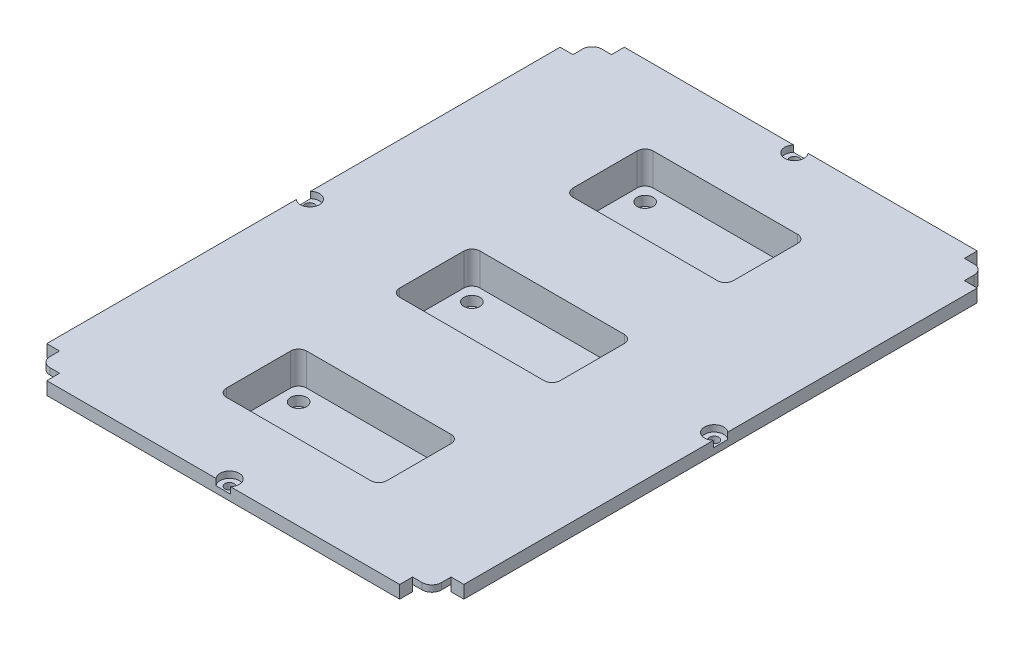
SolidWorks part; units mm, degrees
ref_plane "Спереди" through (0, 0, 0) normal (0, 0, 1) x (1, 0, 0)
ref_plane "Сверху" through (0, 0, 0) normal (0, 1, 0) x (1, 0, 0)
ref_plane "Справа" through (0, 0, 0) normal (1, 0, 0) x (0, 0, -1)
sketch "Эскиз1" plane through (0, 0, 0) normal (0, 1, 0) x (1, 0, 0)
  line L1 (-65, -90) -> (65, -90)
  line L2 (-65, -90) -> (-65, 90)
  line L3 (-65, 90) -> (65, 90)
  line L4 (65, -90) -> (65, 90)
  line L5 (-65, -90) -> (65, 90) construction
  line L6 (-65, 90) -> (65, -90) construction
  point P0 (0, 0)
  dimension "D1" = 130
  dimension "D2" = 180
extrude "Бобышка-Вытянуть1" add sketch "Эскиз1" along normal blind 55
sketch "Эскиз2" plane through (0, 0, 90) normal (0, 0, 1) x (1, 0, 0)
  line L0 (-1050, 27.5) -> (48950, 27.5) construction
  line L1 (-65, 55) -> (-65, 0) construction
  line L2 (0, -999.2777) -> (0, 49000.7223) construction
  line L4 (-22.5, 15) -> (22.5, 15)
  line L5 (-25, 17.5) -> (-25, 37.5)
  line L6 (-22.5, 40) -> (22.5, 40)
  line L7 (25, 17.5) -> (25, 37.5)
  line L8 (-25, 15) -> (25, 40) construction
  line L9 (-25, 40) -> (25, 15) construction
  arc A0 (-22.5, 40) -> (-25, 37.5) centre (-22.5, 37.5) ccw
  arc A1 (-25, 17.5) -> (-22.5, 15) centre (-22.5, 17.5) ccw
  arc A2 (25, 17.5) -> (22.5, 15) centre (22.5, 17.5) cw
  arc A3 (25, 37.5) -> (22.5, 40) centre (22.5, 37.5) ccw
  point P5 (-65, 27.5)
  point P6 (0, 27.5)
  dimension "D3" = 2.5
  dimension "D4" = 2.5
  dimension "D1" = 25
  dimension "D2" = 50
extrude "Вырез-Вытянуть1" cut sketch "Эскиз2" against normal blind 10
sketch "Эскиз4" plane through (0, 55, 0) normal (0, 1, 0) x (1, 0, 0)
  line L0 (0, -1000) -> (0, 49000) construction
  line L1 (-1000, 0) -> (49000, 0) construction
  line L2 (-22.5, 41.5) -> (22.5, 41.5)
  line L3 (-25, 44) -> (-25, 64)
  line L4 (-22.5, 66.5) -> (22.5, 66.5)
  line L5 (-22.5, -12.5) -> (22.5, -12.5)
  line L6 (-25, -10) -> (-25, 10)
  line L7 (-22.5, 12.5) -> (22.5, 12.5)
  line L8 (25, -10) -> (25, 10)
  line L9 (-25, -12.5) -> (25, 12.5) construction
  line L10 (-25, 12.5) -> (25, -12.5) construction
  line L11 (25, 44) -> (25, 64)
  line L12 (-25, 41.5) -> (25, 66.5) construction
  line L13 (-25, 66.5) -> (25, 41.5) construction
  line L14 (-25, -12.5) -> (25, -12.5) [skipped]
  line L15 (-25, -12.5) -> (-25, 12.5) [skipped]
  line L16 (-25, 12.5) -> (25, 12.5) [skipped]
  line L17 (25, -12.5) -> (25, 12.5) [skipped]
  line L18 (-25, -12.5) -> (25, 12.5) construction
  line L19 (-25, 12.5) -> (25, -12.5) construction
  line L20 (-22.5, -66.5) -> (22.5, -66.5)
  line L21 (-25, -64) -> (-25, -44)
  line L22 (-22.5, -41.5) -> (22.5, -41.5)
  line L23 (25, -64) -> (25, -44)
  line L24 (-25, -66.5) -> (25, -41.5) construction
  line L25 (-25, -41.5) -> (25, -66.5) construction
  arc A0 (22.5, -41.5) -> (25, -44) centre (22.5, -44) cw
  arc A1 (25, -64) -> (22.5, -66.5) centre (22.5, -64) cw
  arc A2 (-22.5, -66.5) -> (-25, -64) centre (-22.5, -64) cw
  arc A3 (-25, -44) -> (-22.5, -41.5) centre (-22.5, -44) cw
  arc A4 (-25, 64) -> (-22.5, 66.5) centre (-22.5, 64) cw
  arc A5 (-22.5, 12.5) -> (-25, 10) centre (-22.5, 10) ccw
  arc A6 (25, -10) -> (22.5, -12.5) centre (22.5, -10) cw
  arc A7 (22.5, 66.5) -> (25, 64) centre (22.5, 64) cw
  arc A8 (25, 44) -> (22.5, 41.5) centre (22.5, 44) cw
  arc A9 (-22.5, 41.5) -> (-25, 44) centre (-22.5, 44) cw
  arc A10 (22.5, 12.5) -> (25, 10) centre (22.5, 10) cw
  arc A11 (-22.5, -12.5) -> (-25, -10) centre (-22.5, -10) cw
  point P8 (0, 0)
  point P9 (0, 54)
  point P18 (0, 0)
  point P23 (0, -54)
  dimension "D7" = 2.5
  dimension "D8" = 2.5
  dimension "D1" = 25
  dimension "D2" = 50
  dimension "D5" = 41.5
  dimension "D6" = 41.5
  dimension "D3" = 2
  dimension "D4" = 2
extrude "Вырез-Вытянуть2" cut sketch "Эскиз4" against normal blind 10
mirror "Зеркальное отражение1" about plane through (0, 0, 0) normal (0, 0, 1) of "Вырез-Вытянуть1"
shell "Оболочка1" thickness 4 removed face at (0, 0, 0)
sketch "Эскиз5" plane through (-65, 0, 0) normal (-1, 0, 0) x (0, 0, 1)
  line L0 (45, 28.75) -> (45, 11.25) construction
  line L2 (90, 55) -> (90, 0) construction
  line L4 (-90, 0) -> (90, 0) construction
  line L7 (-1075, 20) -> (48925, 20) construction
  line L8 (-90, 55) -> (-90, 0) construction
  circle A3 centre (45, 28.75) radius 1.45
  circle A4 centre (45, 11.25) radius 1.45
  circle A5 centre (65.6, 20) radius 4
  circle A6 centre (-65.6, 20) radius 5
  dimension "D2" = 17.5
  dimension "D3" = 20
  dimension "D6" = 10
  dimension "D1" = 17.5
  dimension "D5" = 2.9
  dimension "D9" = 45
  dimension "D10" = 20.6
  dimension "D11" = 8
  dimension "D4" = 24.4
extrude "Вырез-Вытянуть3" cut sketch "Эскиз5" against normal blind 15
sketch "Эскиз6" plane through (-65, 0, 0) normal (-1, 0, 0) x (0, 0, 1)
  circle A2 centre (45, 28.75) radius 3
  circle A3 centre (45, 11.25) radius 3
  dimension "D1" = 6
extrude "Вырез-Вытянуть4" cut sketch "Эскиз6" against normal blind 2.5
sketch "Эскиз11" plane through (-61, 0, 0) normal (1, 0, 0) x (0, 0, -1)
  circle A1 centre (-65.6, 20) radius 5
  dimension "D1" = 10
extrude "Вырез-Вытянуть16" cut sketch "Эскиз11" against normal blind 1
mirror "Зеркальное отражение2" about plane through (0, 0, 0) normal (1, 0, 0) of "Вырез-Вытянуть3", "Вырез-Вытянуть4", "Вырез-Вытянуть16"
sketch "Эскиз12" plane through (0, 11, 0) normal (0, -1, 0) x (-1, 0, 0)
  line L0 (-1014.7864, -78) -> (48985.2136, -78) construction
  line L1 (22.5, -76) -> (-22.5, -76) construction
  line L2 (0, -1061) -> (0, 48939) construction
  line L3 (-10, -1061) -> (-10, 48939) construction
  line L4 (10, -1061) -> (10, 48939) construction
  circle A0 centre (-10, -78) radius 1.45
  circle A1 centre (10, -78) radius 1.45
  point P7 (0, -76)
  dimension "D4" = 2.9
  dimension "D1" = 2
  dimension "D2" = 20
  dimension "D3" = 10
extrude "Вырез-Вытянуть17" cut sketch "Эскиз12" against normal blind 14
sketch "Эскиз15" plane through (0, 45, 0) normal (0, 1, 0) x (1, 0, 0)
  line L0 (-1010.1672, -62.5) -> (48989.8328, -62.5) construction
  line L1 (0, -1031.5) -> (0, 48968.5) construction
  line L2 (-7.6, -63.8) -> (7.6, -63.8)
  line L3 (-7.6, -63.8) -> (-7.6, -61.2)
  line L4 (-7.6, -61.2) -> (7.6, -61.2)
  line L5 (7.6, -63.8) -> (7.6, -61.2)
  line L6 (-7.6, -63.8) -> (7.6, -61.2) construction
  line L7 (-7.6, -61.2) -> (7.6, -63.8) construction
  line L8 (22.5, -41.5) -> (-22.5, -41.5) construction
  line L9 (-22.5, -66.5) -> (22.5, -66.5) construction
  line L10 (-7.6, -9.8) -> (7.6, -9.8)
  line L11 (-7.6, -9.8) -> (-7.6, -7.2)
  line L12 (-7.6, -7.2) -> (7.6, -7.2)
  line L13 (7.6, -9.8) -> (7.6, -7.2)
  line L14 (-7.6, -9.8) -> (7.6, -7.2) construction
  line L15 (-7.6, -7.2) -> (7.6, -9.8) construction
  line L16 (-7.6, 44.2) -> (7.6, 44.2)
  line L17 (-7.6, 44.2) -> (-7.6, 46.8)
  line L18 (-7.6, 46.8) -> (7.6, 46.8)
  line L19 (7.6, 44.2) -> (7.6, 46.8)
  line L20 (-7.6, 44.2) -> (7.6, 46.8) construction
  line L21 (-7.6, 46.8) -> (7.6, 44.2) construction
  line L23 (22.5, 12.5) -> (-22.5, 12.5) construction
  line L24 (-7.6, -59.8) -> (7.6, -59.8)
  line L25 (-7.6, -59.8) -> (-7.6, -57.2)
  line L26 (-7.6, -57.2) -> (7.6, -57.2)
  line L27 (7.6, -59.8) -> (7.6, -57.2)
  line L28 (-7.6, -59.8) -> (7.6, -57.2) construction
  line L29 (-7.6, -57.2) -> (7.6, -59.8) construction
  line L30 (-7.6, -5.8) -> (7.6, -5.8)
  line L31 (-7.6, -5.8) -> (-7.6, -3.2)
  line L32 (-7.6, -3.2) -> (7.6, -3.2)
  line L33 (7.6, -5.8) -> (7.6, -3.2)
  line L34 (-7.6, -5.8) -> (7.6, -3.2) construction
  line L35 (-7.6, -3.2) -> (7.6, -5.8) construction
  line L36 (-7.6, 48.2) -> (7.6, 48.2)
  line L37 (-7.6, 48.2) -> (-7.6, 50.8)
  line L38 (-7.6, 50.8) -> (7.6, 50.8)
  line L39 (7.6, 48.2) -> (7.6, 50.8)
  line L40 (-7.6, 48.2) -> (7.6, 50.8) construction
  line L41 (-7.6, 50.8) -> (7.6, 48.2) construction
  line L42 (-22.5, -12.5) -> (22.5, -12.5) construction
  circle A0 centre (-20, -46.5) radius 2.5
  circle A1 centre (20, -46.5) radius 2.5
  circle A2 centre (-20, 7.5) radius 2.5
  circle A3 centre (20, 7.5) radius 2.5
  circle A4 centre (-20, 61.5) radius 2.5
  circle A5 centre (20, 61.5) radius 2.5
  point P1 (0, -62.5)
  point P12 (0, -41.5)
  point P16 (0, -8.5)
  point P21 (0, 45.5)
  point P41 (0, -4.5)
  point P42 (0, -58.5)
  point P51 (0, 49.5)
  dimension "D6" = 40
  dimension "D8" = 5
  dimension "D1" = 2.6
  dimension "D2" = 15.2
  dimension "D3" = 4
  dimension "D4" = 3
  dimension "D5" = 4
  dimension "D7" = 40
  dimension "D9" = 5
  dimension "D10" = 3
  dimension "D11" = 5
  dimension "D13" = 4
  dimension "D15" = 4
  dimension "D12" = 2
  dimension "D14" = 3
extrude "Вырез-Вытянуть20" cut sketch "Эскиз15" against normal blind 3
sketch "Эскиз16" plane through (0, 42, 0) normal (0, 1, 0) x (1, 0, 0)
  line L0 (-7.6, -62.5) -> (7.6, -62.5) construction
  line L1 (-7.6, -61.2) -> (-7.6, -63.8) construction
  line L2 (7.6, -63.8) -> (7.6, -61.2) construction
  line L3 (0, -1000) -> (0, 49000) construction
  line L4 (-7, -63.4) -> (7, -63.4)
  line L5 (-7, -63.4) -> (-7, -61.6)
  line L6 (-7, -61.6) -> (7, -61.6)
  line L7 (7, -63.4) -> (7, -61.6)
  line L8 (-7, -63.4) -> (7, -61.6) construction
  line L9 (-7, -61.6) -> (7, -63.4) construction
  line L10 (-7, -9.4) -> (7, -9.4)
  line L11 (-7, -9.4) -> (-7, -7.6)
  line L12 (-7, -7.6) -> (7, -7.6)
  line L13 (7, -9.4) -> (7, -7.6)
  line L14 (-7.6, -8.5) -> (7.6, -8.5) construction
  line L15 (-7, -9.4) -> (7, -7.6) construction
  line L16 (-7, -7.6) -> (7, -9.4) construction
  line L17 (-7, 44.6) -> (7, 44.6)
  line L18 (-7, 44.6) -> (-7, 46.4)
  line L19 (-7, 46.4) -> (7, 46.4)
  line L20 (7, 44.6) -> (7, 46.4)
  line L21 (-7.6, 45.5) -> (7.6, 45.5) construction
  line L22 (-7, 44.6) -> (7, 46.4) construction
  line L23 (-7, 46.4) -> (7, 44.6) construction
  line L24 (-7.6, -7.2) -> (-7.6, -9.8) construction
  line L25 (-7.6, -58.5) -> (7.6, -58.5) construction
  line L26 (-7, -59.4) -> (7, -59.4)
  line L27 (-7, -59.4) -> (-7, -57.6)
  line L28 (-7, -57.6) -> (7, -57.6)
  line L29 (7, -59.4) -> (7, -57.6)
  line L30 (-7, -59.4) -> (7, -57.6) construction
  line L31 (-7, -57.6) -> (7, -59.4) construction
  line L32 (-7.6, -57.2) -> (-7.6, -59.8) construction
  line L33 (7.6, -59.8) -> (7.6, -57.2) construction
  line L34 (-7.6, -4.5) -> (7.6, -4.5) construction
  line L35 (-7.6, -3.2) -> (-7.6, -5.8) construction
  line L36 (7.6, -5.8) -> (7.6, -3.2) construction
  line L37 (-7.6, -9.8) -> (7.6, -9.8) construction
  line L38 (-7, -5.4) -> (7, -5.4)
  line L39 (-7, -5.4) -> (-7, -3.6)
  line L40 (-7, -3.6) -> (7, -3.6)
  line L41 (7, -5.4) -> (7, -3.6)
  line L42 (-7, -5.4) -> (7, -3.6) construction
  line L43 (-7, -3.6) -> (7, -5.4) construction
  line L44 (7.6, -9.8) -> (7.6, -7.2) construction
  line L45 (-7.6, 46.8) -> (-7.6, 44.2) construction
  line L46 (7.6, 44.2) -> (7.6, 46.8) construction
  line L47 (-7.6, 44.2) -> (7.6, 44.2) construction
  line L48 (-7.6, 49.5) -> (7.6, 49.5) construction
  line L49 (-7.6, 50.8) -> (-7.6, 48.2) construction
  line L50 (7.6, 48.2) -> (7.6, 50.8) construction
  line L52 (-7, 48.6) -> (7, 48.6)
  line L53 (-7, 48.6) -> (-7, 50.4)
  line L54 (-7, 50.4) -> (7, 50.4)
  line L55 (7, 48.6) -> (7, 50.4)
  line L56 (-7, 48.6) -> (7, 50.4) construction
  line L57 (-7, 50.4) -> (7, 48.6) construction
  point P6 (0, -62.5)
  point P12 (0, -58.5)
  point P17 (0, -8.5)
  point P24 (0, 36.6)
  point P41 (0, -4.5)
  point P54 (0, 49.5)
  dimension "D1" = 1.8
  dimension "D2" = 14
  dimension "D4" = 0.4
  dimension "D3" = 0.4
extrude "Вырез-Вытянуть21" cut sketch "Эскиз16" against normal blind 3
sketch "Эскиз17" plane through (0, 0, 80) normal (0, 0, 1) x (1, 0, 0)
  line L0 (-7.6, 17.5) -> (7.6, 17.5)
  line L1 (-7.6, 17.5) -> (-7.6, 20.1)
  line L2 (-7.6, 20.1) -> (7.6, 20.1)
  line L3 (7.6, 17.5) -> (7.6, 20.1)
  line L4 (-7.6, 17.5) -> (7.6, 20.1) construction
  line L5 (-7.6, 20.1) -> (7.6, 17.5) construction
  line L7 (-7.6, 21.5) -> (7.6, 21.5)
  line L8 (-22.5, 15) -> (22.5, 15) construction
  line L9 (0, -965) -> (0, 49035) construction
  line L10 (22.5, 40) -> (-22.5, 40) construction
  line L11 (-7.6, 21.5) -> (-7.6, 24.1)
  line L12 (-7.6, 24.1) -> (7.6, 24.1)
  line L13 (7.6, 21.5) -> (7.6, 24.1)
  line L14 (-7.6, 21.5) -> (7.6, 24.1) construction
  line L15 (-7.6, 24.1) -> (7.6, 21.5) construction
  circle A0 centre (-20, 35) radius 2.5
  circle A1 centre (20, 35) radius 2.5
  point P0 (0, 18.8)
  point P11 (0, 22.8)
  point P20 (0, 40)
  dimension "D5" = 5
  dimension "D8" = 4
  dimension "D1" = 2.6
  dimension "D2" = 15.2
  dimension "D3" = 40
  dimension "D4" = 40
  dimension "D6" = 2.5
  dimension "D7" = 5
extrude "Вырез-Вытянуть22" cut sketch "Эскиз17" against normal blind 3
sketch "Эскиз18" plane through (0, 0, 77) normal (0, 0, 1) x (1, 0, 0)
  line L0 (-7.6, 18.8) -> (7.6, 18.8) construction
  line L1 (-7.6, 20.1) -> (-7.6, 17.5) construction
  line L2 (7.6, 17.5) -> (7.6, 20.1) construction
  line L3 (0, -980.9) -> (0, 49019.1) construction
  line L4 (-7, 17.9) -> (7, 17.9)
  line L5 (-7, 17.9) -> (-7, 19.7)
  line L6 (-7, 19.7) -> (7, 19.7)
  line L7 (7, 17.9) -> (7, 19.7)
  line L8 (-7, 17.9) -> (7, 19.7) construction
  line L9 (-7, 19.7) -> (7, 17.9) construction
  line L10 (7.6, 24.1) -> (-7.6, 24.1) construction
  line L12 (-7, 21.9) -> (7, 21.9)
  line L13 (-7, 21.9) -> (-7, 23.7)
  line L14 (-7, 23.7) -> (7, 23.7)
  line L15 (7, 21.9) -> (7, 23.7)
  line L16 (-7, 21.9) -> (7, 23.7) construction
  line L17 (-7, 23.7) -> (7, 21.9) construction
  point P6 (0, 18.8)
  point P12 (0, 22.8)
  point P16 (0, 24.1)
  dimension "D1" = 1.8
  dimension "D2" = 14
  dimension "D3" = 4
extrude "Вырез-Вытянуть23" cut sketch "Эскиз18" against normal blind 3
sketch "Эскиз19" plane through (0, 0, -80) normal (0, 0, -1) x (1, 0, 0)
  line L0 (-7.6, -37.5) -> (7.6, -37.5)
  line L1 (-7.6, -37.5) -> (-7.6, -34.9)
  line L2 (-7.6, -34.9) -> (7.6, -34.9)
  line L3 (7.6, -37.5) -> (7.6, -34.9)
  line L4 (-7.6, -37.5) -> (7.6, -34.9) construction
  line L5 (-7.6, -34.9) -> (7.6, -37.5) construction
  line L6 (0, -1010) -> (0, 48990) construction
  line L7 (-22.5, -15) -> (22.5, -15) construction
  line L9 (-7.6, -33.5) -> (7.6, -33.5)
  line L10 (22.5, -40) -> (-22.5, -40) construction
  line L11 (-7.6, -33.5) -> (-7.6, -30.9)
  line L12 (-7.6, -30.9) -> (7.6, -30.9)
  line L13 (7.6, -33.5) -> (7.6, -30.9)
  line L14 (-7.6, -33.5) -> (7.6, -30.9) construction
  line L15 (-7.6, -30.9) -> (7.6, -33.5) construction
  circle A0 centre (-20, -20) radius 2.5
  circle A1 centre (20, -20) radius 2.5
  point P0 (0, -36.2)
  point P14 (0, -15)
  point P16 (0, -32.2)
  dimension "D5" = 5
  dimension "D7" = 2.5
  dimension "D1" = 2.6
  dimension "D2" = 15.2
  dimension "D3" = 40
  dimension "D4" = 40
  dimension "D6" = 5
  dimension "D8" = 4
extrude "Вырез-Вытянуть24" cut sketch "Эскиз19" against normal blind 3
sketch "Эскиз20" plane through (0, 0, -77) normal (0, 0, -1) x (1, 0, 0)
  line L0 (-1007.6, -36.2) -> (48992.4, -36.2) construction
  line L1 (-7.6, -34.9) -> (-7.6, -37.5) construction
  line L3 (-7, -37.1) -> (7, -37.1)
  line L4 (-7, -37.1) -> (-7, -35.3)
  line L5 (-7, -35.3) -> (7, -35.3)
  line L6 (7, -37.1) -> (7, -35.3)
  line L7 (-7, -37.1) -> (7, -35.3) construction
  line L8 (-7, -35.3) -> (7, -37.1) construction
  line L9 (-7, -31.3) -> (7, -31.3)
  line L10 (0, -1029.9) -> (0, 48970.1) construction
  line L11 (7.6, -34.9) -> (-7.6, -34.9) construction
  line L12 (-7, -31.3) -> (-7, -33.1)
  line L13 (-7, -33.1) -> (7, -33.1)
  line L14 (7, -31.3) -> (7, -33.1)
  line L15 (-7, -31.3) -> (7, -33.1) construction
  line L16 (-7, -33.1) -> (7, -31.3) construction
  point P1 (0, -36.2)
  point P5 (-7.6, -36.2)
  point P10 (0, -32.2)
  point P18 (0, -34.9)
  dimension "D1" = 1.8
  dimension "D2" = 14
  dimension "D3" = 4
extrude "Вырез-Вытянуть25" cut sketch "Эскиз20" against normal blind 5
sketch "Эскиз21" plane through (0, 0, 90) normal (0, 0, -1) x (1, 0, 0)
  line L0 (-975, -27.5) -> (49025, -27.5) construction
  line L1 (35.25, -34.75) -> (44.75, -34.75)
  line L2 (35.25, -34.75) -> (35.25, -20.25)
  line L3 (35.25, -20.25) -> (44.75, -20.25)
  line L4 (44.75, -34.75) -> (44.75, -20.25)
  line L5 (35.25, -34.75) -> (44.75, -20.25) construction
  line L6 (35.25, -20.25) -> (44.75, -34.75) construction
  line L7 (25, -17.5) -> (25, -37.5) construction
  line L8 (40, -1022.5) -> (40, 48977.5) construction
  line L9 (65, -55) -> (65, 0) construction
  point P0 (40, -27.5)
  point P10 (25, -27.5)
  dimension "D1" = 9.5
  dimension "D2" = 14.5
  dimension "D3" = 25
extrude "Вырез-Вытянуть26" cut sketch "Эскиз21" along normal blind 4
sketch "Эскиз22" plane through (0, 0, 0) normal (0, -1, 0) x (-1, 0, 0)
  line L0 (-63, -925) -> (-63, 49075) construction
  line L2 (-65, -90) -> (-65, 90) construction
  line L3 (-1046.2998, 88) -> (48953.7002, 88) construction
  line L4 (-65, 90) -> (65, 90) construction
  line L5 (63, -925) -> (63, 49075) construction
  line L6 (65, 90) -> (65, -90) construction
  line L7 (-1052.5, -88) -> (48947.5, -88) construction
  line L8 (65, -90) -> (-65, -90) construction
  line L9 (0, -925) -> (0, 49075) construction
  line L10 (-1052.5, 0) -> (48947.5, 0) construction
  circle A4 centre (0, 88) radius 1.425
  circle A5 centre (0, -88) radius 1.425
  circle A6 centre (-63, 0) radius 1.425
  circle A7 centre (63, 0) radius 1.425
  point P27 (0, 90)
  point P34 (-65, 0)
  dimension "D5" = 2.85
  dimension "D1" = 2
  dimension "D2" = 2
  dimension "D3" = 2
  dimension "D4" = 2
extrude "Вырез-Вытянуть27" cut sketch "Эскиз22" against normal blind 9
sketch "Эскиз24" plane through (-65, 0, 0) normal (-1, 0, 0) x (0, 0, 1)
  line L0 (0, -1000) -> (0, 49000) construction
  line L1 (16, -988.2808) -> (16, 49011.7192) construction
  line L2 (-90, 0) -> (90, 0) construction
  circle A0 centre (16, 16) radius 1.475
  circle A1 centre (16, 27.5) radius 1.475
  dimension "D4" = 2.95
  dimension "D1" = 11.5
  dimension "D2" = 16
  dimension "D3" = 16
extrude "Вырез-Вытянуть28" cut sketch "Эскиз24" against normal through all
fillet "Скругление1" radius 10 4 edges at (65, 27.5, -90) (-65, 27.5, -90) (65, 27.5, 90) (-65, 27.5, 90)
sketch "Эскиз26" plane through (61, 0, 0) normal (-1, 0, 0) x (0, 0, 1)
  line L1 (17.6454, 18.85) -> (14.3546, 18.85)
  line L2 (14.3546, 18.85) -> (12.7091, 16)
  line L3 (12.7091, 16) -> (14.3546, 13.15)
  line L4 (14.3546, 13.15) -> (17.6454, 13.15)
  line L5 (17.6454, 13.15) -> (19.2909, 16)
  line L6 (19.2909, 16) -> (17.6454, 18.85)
  line L7 (17.6454, 30.35) -> (14.3546, 30.35)
  line L8 (14.3546, 30.35) -> (12.7091, 27.5)
  line L9 (12.7091, 27.5) -> (14.3546, 24.65)
  line L10 (14.3546, 24.65) -> (17.6454, 24.65)
  line L11 (17.6454, 24.65) -> (19.2909, 27.5)
  line L12 (19.2909, 27.5) -> (17.6454, 30.35)
  circle A0 centre (16, 16) radius 2.85 construction
  circle A1 centre (16, 27.5) radius 2.85 construction
  dimension "D1" = 5.7
extrude "Вырез-Вытянуть29" cut sketch "Эскиз26" against normal blind 2 and the other way blind 124
fillet "Скругление2" radius 3 4 edges at (61, 25.5, 86) (61, 25.5, -86) (-61, 25.5, -86) (-61, 25.5, 86)
sketch "Эскиз27" plane through (0, 0, 0) normal (0, -1, 0) x (1, 0, 0)
  line L0 (-55, -90) -> (-45, -90)
  line L1 (55, -90) -> (-55, -90) construction
  line L2 (-45, -90) -> (-45, -86)
  line L3 (58, -86) -> (-58, -86) construction
  line L4 (-45, -86) -> (-58, -86)
  line L6 (-61, -83) -> (-61, -70)
  line L7 (-61, -83) -> (-61, 83) construction
  line L8 (-61, -70) -> (-65, -70)
  line L9 (-65, -80) -> (-65, 80) construction
  line L10 (-65, -70) -> (-65, -80)
  line L11 (0, -1000) -> (0, 49000) construction
  line L12 (-1000, 0) -> (49000, 0) construction
  line L13 (65, -70) -> (65, -80)
  line L14 (61, -70) -> (65, -70)
  line L15 (61, -83) -> (61, -70)
  line L16 (45, -86) -> (58, -86)
  line L17 (45, -90) -> (45, -86)
  line L18 (55, -90) -> (45, -90)
  line L19 (55, 90) -> (45, 90)
  line L20 (45, 90) -> (45, 86)
  line L21 (45, 86) -> (58, 86)
  line L22 (61, 83) -> (61, 70)
  line L23 (61, 70) -> (65, 70)
  line L24 (65, 70) -> (65, 80)
  line L25 (-65, 70) -> (-65, 80)
  line L26 (-61, 70) -> (-65, 70)
  line L27 (-61, 83) -> (-61, 70)
  line L28 (-45, 86) -> (-58, 86)
  line L29 (-45, 90) -> (-45, 86)
  line L30 (-55, 90) -> (-45, 90)
  arc A1 (-65, -80) -> (-55, -90) centre (-55, -80) ccw construction
  arc A4 (61, -83) -> (58, -86) centre (58, -83) cw
  arc A5 (-65, -80) -> (-55, -90) centre (-55, -80) ccw
  arc A6 (65, -80) -> (55, -90) centre (55, -80) cw
  arc A7 (-61, 83) -> (-58, 86) centre (-58, 83) cw
  arc A8 (-61, -83) -> (-58, -86) centre (-58, -83) ccw construction
  arc A9 (-61, -83) -> (-58, -86) centre (-58, -83) ccw
  arc A10 (65, 80) -> (55, 90) centre (55, 80) ccw
  arc A11 (-65, 80) -> (-55, 90) centre (-55, 80) cw
  arc A12 (61, 83) -> (58, 86) centre (58, 83) ccw
  dimension "D1" = 10
extrude "Бобышка-Вытянуть2" add sketch "Эскиз27" along normal blind 3
sketch "Эскиз28" plane through (0, 0, 0) normal (0, -1, 0) x (1, 0, 0)
  line L0 (-61, 70) -> (-61, 83) construction
  line L2 (-61, 70) -> (-61, 83)
  line L3 (-58, 86) -> (-45, 86)
  line L4 (-45, 86) -> (-45, 86.5)
  line L5 (-45, 86) -> (-45, 90) construction
  line L6 (-45, 86.5) -> (-58, 86.5)
  line L7 (-1000, 0) -> (49000, 0) construction
  line L8 (-61.5, 83) -> (-61.5, 70)
  line L9 (-65, 70) -> (-61, 70) construction
  line L10 (-61.5, 70) -> (-61, 70)
  line L11 (0, -1000) -> (0, 49000) construction
  line L12 (61.5, 70) -> (61, 70)
  line L13 (61.5, 83) -> (61.5, 70)
  line L14 (45, 86.5) -> (58, 86.5)
  line L15 (45, 86) -> (45, 86.5)
  line L16 (58, 86) -> (45, 86)
  line L17 (61, 70) -> (61, 83)
  line L18 (61, -70) -> (61, -83)
  line L19 (58, -86) -> (45, -86)
  line L20 (45, -86) -> (45, -86.5)
  line L21 (45, -86.5) -> (58, -86.5)
  line L22 (61.5, -83) -> (61.5, -70)
  line L23 (61.5, -70) -> (61, -70)
  line L24 (-61.5, -70) -> (-61, -70)
  line L25 (-61.5, -83) -> (-61.5, -70)
  line L26 (-45, -86.5) -> (-58, -86.5)
  line L27 (-45, -86) -> (-45, -86.5)
  line L28 (-58, -86) -> (-45, -86)
  line L29 (-61, -70) -> (-61, -83)
  arc A0 (-58, 86) -> (-61, 83) centre (-58, 83) ccw construction
  arc A1 (-58, 86) -> (-61, 83) centre (-58, 83) ccw
  arc A2 (-61.5, 83) -> (-58, 86.5) centre (-58, 83) cw
  arc A3 (61.5, 83) -> (58, 86.5) centre (58, 83) ccw
  arc A4 (58, 86) -> (61, 83) centre (58, 83) cw
  arc A5 (58, -86) -> (61, -83) centre (58, -83) ccw
  arc A6 (61.5, -83) -> (58, -86.5) centre (58, -83) cw
  arc A7 (-61.5, -83) -> (-58, -86.5) centre (-58, -83) ccw
  arc A8 (-58, -86) -> (-61, -83) centre (-58, -83) cw
  dimension "D1" = 0.5
extrude "Вырез-Вытянуть30" cut sketch "Эскиз28" along normal blind 2.5
sketch "Эскиз30" plane through (0, 51, 0) normal (0, -1, 0) x (1, 0, 0)
  line L0 (-29, -10) -> (-29, 10) construction
  line L1 (-58.5, 86) -> (-29, 86)
  line L2 (-61, 83.5) -> (-61, 6)
  line L3 (-61, 6) -> (-29, 6)
  line L4 (-29, 86) -> (-29, 6)
  line L5 (-58, 86) -> (58, 86) construction
  line L6 (-61, -83) -> (-61, 83) construction
  line L7 (0, -1000) -> (0, 49000) construction
  line L8 (29, 86) -> (29, 6)
  line L9 (61, 6) -> (29, 6)
  line L10 (61, 83.5) -> (61, 6)
  line L11 (58.5, 86) -> (29, 86)
  arc A0 (-58.5, 86) -> (-61, 83.5) centre (-58.5, 83.5) ccw
  arc A1 (58.5, 86) -> (61, 83.5) centre (58.5, 83.5) cw
  dimension "D1" = 2.5
  dimension "D2" = 80
extrude "Вырез-Вытянуть32" cut sketch "Эскиз30" against normal blind 2
sketch "Эскиз29" plane through (-61, 0, 0) normal (1, 0, 0) x (0, 0, -1)
  line L1 (83, 51) -> (-6, 51) construction
  line L2 (-86, 0) -> (-86, 51) construction
  line L3 (0, -1000) -> (0, 49000) construction
  line L4 (90, 55) -> (90, -3) construction
  line L6 (-80, 55) -> (80, 55) construction
  circle A0 centre (-73.5, 43) radius 1.45
  circle A1 centre (-18.5, 43) radius 1.45
  circle A4 centre (18.5, 41) radius 1.45
  circle A5 centre (73.5, 41) radius 1.45
  dimension "D1" = 8
  dimension "D4" = 2.9
  dimension "D5" = 55
  dimension "D2" = 12.5
  dimension "D3" = 55
  dimension "D6" = 16.5
  dimension "D7" = 14
extrude "Вырез-Вытянуть31" cut sketch "Эскиз29" against normal through all both and the other way through all
sketch "Эскиз31" plane through (0, 41, 0) normal (0, -1, 0) x (1, 0, 0)
  line L0 (26, -1043.9084) -> (26, 48956.0916) construction
  line L2 (29, 64) -> (29, 44) construction
  line L3 (29, -76) -> (29, -86) construction
  line L4 (26, 81) -> (29, 81)
  line L5 (26, 81) -> (26, -81)
  line L6 (26, -81) -> (29, -81)
  line L7 (29, 81) -> (29, -81)
  line L8 (22.5, 76) -> (22.5, 86) construction
  line L9 (-977.5, 81) -> (49022.5, 81) construction
  line L10 (0, -1000) -> (0, 49000) construction
  line L11 (-26, -1043.9084) -> (-26, 48956.0916) construction
  line L12 (-29, 81) -> (-29, -81)
  line L13 (-26, -81) -> (-29, -81)
  line L14 (-26, 81) -> (-26, -81)
  line L15 (-26, 81) -> (-29, 81)
  point P16 (22.5, 81)
  dimension "D1" = 3
extrude "Вырез-Вытянуть33" cut sketch "Эскиз31" against normal up to surface (10 mm away) and the other way blind 20 up to face at (0, 51, 27)
sketch "Эскиз32" plane through (61, 0, 0) normal (-1, 0, 0) x (0, 0, 1)
  line L0 (-83, 51) -> (-83, 0) construction
  line L1 (-83, 7) -> (-81.5, 7)
  line L2 (-83, 7) -> (-83, 24.5)
  line L3 (-83, 24.5) -> (-81.5, 24.5)
  line L4 (-81.5, 7) -> (-81.5, 24.5)
  line L5 (83, 0) -> (-83, 0) construction
  dimension "D1" = 17.5
  dimension "D2" = 1.5
  dimension "D3" = 7
extrude "Вырез-Вытянуть34" cut sketch "Эскиз32" against normal blind 3 contours L1 L4 L3 L2
sketch "Эскиз33" plane through (61, 0, 0) normal (-1, 0, 0) x (0, 0, 1)
  line L0 (-81.5, 7) -> (-81.5, 24.5) construction
  line L1 (-82.5, 20.75) -> (-78.5, 20.75)
  line L2 (-82.5, 20.75) -> (-82.5, 10.75)
  line L3 (-82.5, 10.75) -> (-78.5, 10.75)
  line L4 (-78.5, 20.75) -> (-78.5, 10.75)
  line L5 (-1081.5, 15.75) -> (48918.5, 15.75) construction
  point P7 (-78.5, 15.75)
  point P9 (-81.5, 15.75)
  dimension "D1" = 10
  dimension "D2" = 4
  dimension "D3" = 3
extrude "Вырез-Вытянуть35" cut sketch "Эскиз33" against normal blind 4
sketch "Эскиз34" plane through (0, 0, -86) normal (0, 0, 1) x (1, 0, 0)
  line L0 (61, 51) -> (61, 24.5) construction
  line L1 (34, 7) -> (61, 7)
  line L2 (34, 7) -> (34, 24.5)
  line L3 (34, 24.5) -> (61, 24.5)
  line L4 (61, 7) -> (61, 24.5)
  line L5 (58, 0) -> (-58, 0) construction
  dimension "D1" = 7
  dimension "D2" = 27
  dimension "D3" = 17.5
extrude "Бобышка-Вытянуть3" add sketch "Эскиз34" along normal blind 3
sketch "Эскиз35" plane through (61, 0, 0) normal (-1, 0, 0) x (0, 0, 1)
  line L0 (-90, 55) -> (-90, -3) construction
  line L1 (83, 0) -> (-83, 0) construction
  circle A0 centre (-50, 23.5) radius 1.45
  circle A1 centre (-19.5, 7.5) radius 1.45
  dimension "D1" = 16
  dimension "D5" = 2.9
  dimension "D2" = 30.5
  dimension "D3" = 40
  dimension "D4" = 7.5
extrude "Вырез-Вытянуть36" cut sketch "Эскиз35" against normal blind 4
sketch "Эскиз36" plane through (0, 41, 0) normal (0, -1, 0) x (1, 0, 0)
  line L0 (-22.5, 16.5) -> (22.5, 16.5) construction
  line L1 (-17.5, 16.5) -> (17.5, 16.5)
  line L2 (-17.5, 16.5) -> (-17.5, 21.5)
  line L3 (-17.5, 21.5) -> (17.5, 21.5)
  line L4 (17.5, 16.5) -> (17.5, 21.5)
  line L5 (0, -990.6) -> (0, 49009.4) construction
  line L6 (-7, 9.4) -> (7, 9.4) construction
  point P7 (0, 21.5)
  point P11 (0, 9.4)
  dimension "D1" = 5
  dimension "D2" = 35
extrude "Бобышка-Вытянуть4" add sketch "Эскиз36" against normal up to surface (10 mm away)
sketch "Эскиз37" plane through (0, 41, 0) normal (0, -1, 0) x (1, 0, 0)
  line L0 (-14.5, -981.9998) -> (-14.5, 49018.0002) construction
  line L1 (14.5, -981.9998) -> (14.5, 49018.0002) construction
  line L2 (17.5, 21.5) -> (-17.5, 21.5) construction
  circle A0 centre (-14.5, 19.5) radius 1.45
  circle A1 centre (14.5, 19.5) radius 1.45
  dimension "D3" = 2.9
  dimension "D1" = 29
  dimension "D2" = 14.5
  dimension "D4" = 2
extrude "Вырез-Вытянуть37" cut sketch "Эскиз37" against normal blind 6
sketch "Эскиз38" plane through (-61, 0, 0) normal (1, 0, 0) x (0, 0, -1)
  line L0 (-3.9, -995.0619) -> (-3.9, 49004.9381) construction
  line L1 (52, -995.0619) -> (52, 49004.9381) construction
  line L2 (-1004.5398, 26.8) -> (48995.4602, 26.8) construction
  line L3 (-1004.5398, 8) -> (48995.4602, 8) construction
  line L4 (83, 0) -> (-83, 0) construction
  line L5 (86, 51) -> (86, 0) construction
  circle A0 centre (-3.9, 26.8) radius 1.45
  circle A1 centre (-3.9, 8) radius 1.45
  circle A2 centre (52, 8) radius 1.45
  circle A3 centre (52, 26.8) radius 1.45
  dimension "D3" = 2.9
  dimension "D1" = 55.9
  dimension "D2" = 18.8
  dimension "D4" = 8
  dimension "D5" = 34
extrude "Вырез-Вытянуть38" cut sketch "Эскиз38" against normal blind 10
sketch "Эскиз39" plane through (0, 41, 0) normal (0, -1, 0) x (1, 0, 0)
  line L1 (-26, -4) -> (-21, -4)
  line L2 (-26, -4) -> (-26, -11.5)
  line L3 (-26, -11.5) -> (-21, -11.5)
  line L4 (-21, -4) -> (-21, -11.5)
  line L5 (-26, -15.4772) -> (-26, 15.4772) construction
  line L6 (22.5, -16.5) -> (-22.5, -16.5) construction
  line L7 (-26, -38.5228) -> (-26, -69.4772) construction
  line L8 (-26, -61) -> (-21, -61)
  line L9 (-26, -61) -> (-26, -68.5)
  line L10 (-26, -68.5) -> (-21, -68.5)
  line L11 (-21, -61) -> (-21, -68.5)
  line L12 (22.5, -70.5) -> (-22.5, -70.5) construction
  line L13 (0, -1000) -> (0, 49000) construction
  line L14 (21, -61) -> (21, -68.5)
  line L15 (26, -68.5) -> (21, -68.5)
  line L16 (26, -61) -> (26, -68.5)
  line L17 (26, -61) -> (21, -61)
  line L18 (21, -4) -> (21, -11.5)
  line L19 (26, -11.5) -> (21, -11.5)
  line L20 (26, -4) -> (26, -11.5)
  line L21 (26, -4) -> (21, -4)
  dimension "D1" = 5
  dimension "D2" = 5
  dimension "D3" = 7.5
  dimension "D4" = 2
  dimension "D5" = 7.5
extrude "Бобышка-Вытянуть5" add sketch "Эскиз39" along normal blind 10
sketch "Эскиз40" plane through (0, 31, 0) normal (0, -1, 0) x (1, 0, 0)
  line L0 (0, -1000) -> (0, 49000) construction
  line L1 (-24.5, -1009.0693) -> (-24.5, 48990.9307) construction
  line L2 (-26, -68.5) -> (-21, -68.5) construction
  circle A0 centre (-24.5, -8.5) radius 1.45
  circle A1 centre (-24.5, -66) radius 1.45
  circle A2 centre (24.5, -66) radius 1.45
  circle A3 centre (24.5, -8.5) radius 1.45
  dimension "D2" = 57.5
  dimension "D4" = 2.9
  dimension "D1" = 24.5
  dimension "D3" = 2.5
extrude "Вырез-Вытянуть39" cut sketch "Эскиз40" against normal blind 6
sketch "Эскиз41" plane through (0, 55, 0) normal (0, 1, 0) x (1, 0, 0)
  line L0 (-65, 80) -> (-61, 80)
  line L1 (-55, 90) -> (-55, 86)
  line L2 (-994.6514, 0) -> (49005.3486, 0) construction
  line L3 (-55, 86) -> (-58, 86)
  line L8 (-61, 80) -> (-61, 83)
  line L9 (-61, -80) -> (-61, -83)
  line L10 (-55, -86) -> (-58, -86)
  line L11 (-55, -90) -> (-55, -86)
  line L12 (-65, -80) -> (-61, -80)
  line L13 (0, -998.509) -> (0, 49001.491) construction
  line L14 (65, -80) -> (61, -80)
  line L15 (55, -90) -> (55, -86)
  line L16 (55, -86) -> (58, -86)
  line L17 (61, -80) -> (61, -83)
  line L18 (61, 80) -> (61, 83)
  line L19 (55, 86) -> (58, 86)
  line L20 (55, 90) -> (55, 86)
  line L21 (65, 80) -> (61, 80)
  arc A0 (-55, 90) -> (-65, 80) centre (-55, 80) ccw
  arc A1 (-61, 83) -> (-58, 86) centre (-58, 83) cw
  arc A2 (-61, -83) -> (-58, -86) centre (-58, -83) ccw
  arc A3 (-55, -90) -> (-65, -80) centre (-55, -80) cw
  arc A4 (55, -90) -> (65, -80) centre (55, -80) ccw
  arc A5 (61, -83) -> (58, -86) centre (58, -83) cw
  arc A6 (61, 83) -> (58, 86) centre (58, 83) ccw
  arc A7 (55, 90) -> (65, 80) centre (55, 80) cw
  arc A8 (-55, 90) -> (-65, 80) centre (-55, 80) ccw construction
  point P44 (-60.9423, 81.0728)
  point P46 (-56.2969, 89.9155)
  dimension "D2" = 3
  dimension "D1" = 4
extrude "Вырез-Вытянуть41" cut sketch "Эскиз41" against normal blind 40
sketch "Эскиз42" plane through (0, 51, 0) normal (0, -1, 0) x (1, 0, 0)
  line L1 (-76.2053, 94.5466) -> (89.9317, 94.5466)
  line L2 (-76.2053, 94.5466) -> (-76.2053, -96.6766)
  line L3 (-76.2053, -96.6766) -> (89.9317, -96.6766)
  line L4 (89.9317, 94.5466) -> (89.9317, -96.6766)
  line L5 (-34.5527, 72.3003) -> (43.3092, 72.3003)
  line L6 (-34.5527, 72.3003) -> (-34.5527, -73.247)
  line L7 (-34.5527, -73.247) -> (43.3092, -73.247)
  line L8 (43.3092, 72.3003) -> (43.3092, -73.247)
extrude "Вырез-Вытянуть42" cut sketch "Эскиз42" along normal blind 91
sketch "Эскиз43" plane through (0, 55, 0) normal (0, 1, 0) x (1, 0, 0)
  line L0 (0, -910) -> (0, 49090) construction
  line L1 (55, 90) -> (-55, 90) construction
  line L2 (-935, 0) -> (49065, 0) construction
  line L3 (65, -80) -> (65, 80) construction
  circle A0 centre (0, 88) radius 1.45
  circle A1 centre (0, -88) radius 1.45
  circle A2 centre (63, 0) radius 1.45
  circle A3 centre (-63, 0) radius 1.45
  point P5 (0, 90)
  point P10 (65, 0)
  dimension "D1" = 2
  dimension "D2" = 2.9
  dimension "D3" = 2
  dimension "D4" = 2.9
extrude "Вырез-Вытянуть43" cut sketch "Эскиз43" against normal blind 4
sketch "Эскиз44" plane through (0, 55, 0) normal (0, 1, 0) x (1, 0, 0)
  circle A0 centre (-63, 0) radius 3
  circle A1 centre (0, 88) radius 3
  circle A2 centre (63, 0) radius 3
  circle A3 centre (0, -88) radius 3
  circle A5 centre (0, -88) radius 1.45 construction
  circle A6 centre (-63, 0) radius 1.45 construction
  circle A7 centre (0, 88) radius 1.45 construction
  circle A8 centre (63, 0) radius 1.45 construction
  dimension "D1" = 6
extrude "Вырез-Вытянуть44" cut sketch "Эскиз44" against normal blind 2
sketch "Эскиз45" plane through (0, 0, 37.5) normal (0, 0, -1) x (-1, 0, 0)
  line L0 (-22.5, 51) -> (22.5, 51) construction
  line L1 (-10, 51) -> (10, 51)
  line L2 (-10, 51) -> (-10, 43.5)
  line L3 (-10, 43.5) -> (10, 43.5)
  line L4 (10, 51) -> (10, 43.5)
  line L5 (0, -947) -> (0, 49053) construction
  line L6 (-2.2361, 53) -> (2.2361, 53) construction
  point P11 (0, 53)
  dimension "D1" = 7.5
  dimension "D2" = 20
extrude "Вырез-Вытянуть45" cut sketch "Эскиз45" against normal blind 2
